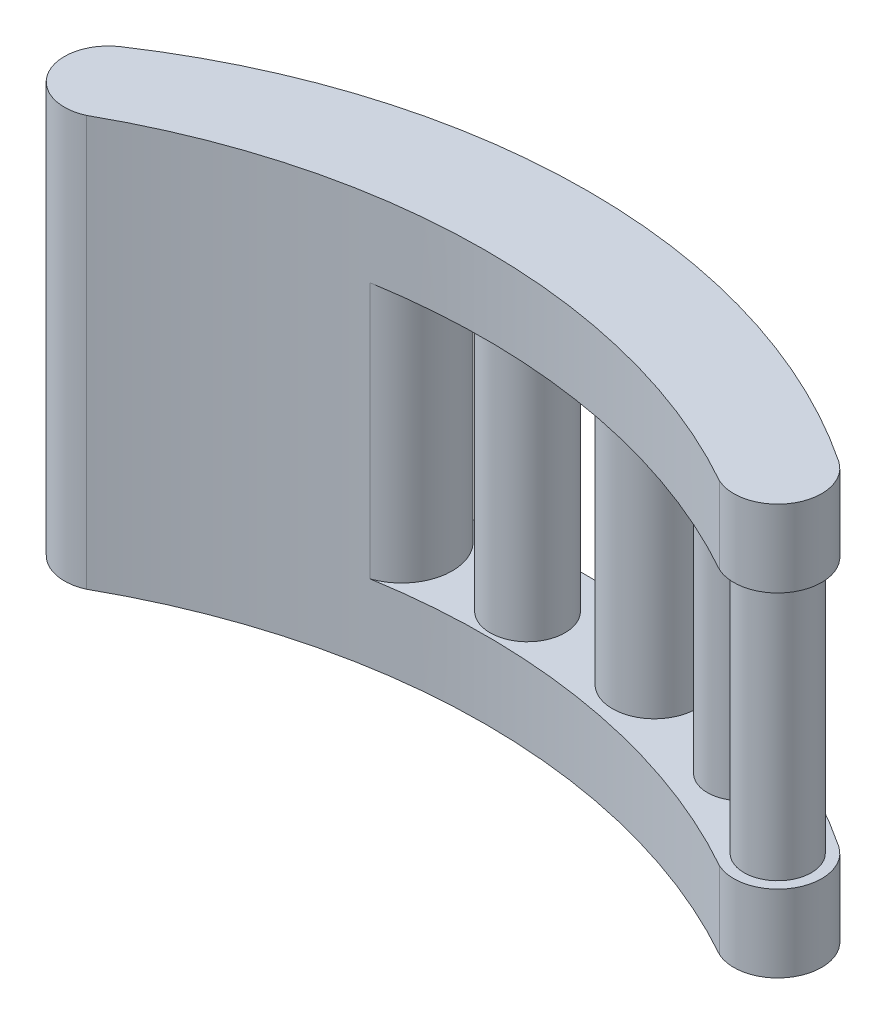
SolidWorks part; units mm, degrees
ref_plane "Front Plane" through (0, 0, 0) normal (0, 0, 1) x (1, 0, 0)
ref_plane "Top Plane" through (0, 0, 0) normal (0, 1, 0) x (1, 0, 0)
ref_plane "Right Plane" through (0, 0, 0) normal (1, 0, 0) x (0, 0, -1)
ref_plane "Plane1" through (0, 20, 0) normal (0, 1, 0) x (1, 0, 0)
sketch "Sketch1" plane through (0, 0, 0) normal (0, 1, 0) x (1, 0, 0)
  line L0 (0, 0) -> (0, -52.5) construction
  line L1 (0, 0) -> (-35, 0) construction
  line L2 (0, 0) -> (35, 0) construction
  line L3 (0, 10.5971) -> (0, 0.5971) construction
  line L4 (0, -52.5) -> (0, -62.5) construction
  line L5 (-35, 0) -> (-35, -10) construction
  line L6 (35, 0) -> (35, -10) construction
  arc A0 (35, 0) -> (-35, 0) centre (0, -52.5) ccw
  arc A1 (30.8661, -7.4679) -> (-30.8661, -7.4679) centre (0, -62.5) ccw
  arc A2 (-35, 0) -> (-30.2491, -7.1263) centre (-32.6246, -3.5632) ccw
  arc A3 (35, 0) -> (30.2491, -7.1263) centre (32.6246, -3.5632) cw
  dimension "D1" = 52.5
  dimension "D2" = 35
  dimension "D3" = 35
  dimension "D4" = 10
  dimension "D5" = 10
  dimension "D6" = 10
extrude "Boss-Extrude1" add sketch "Sketch1" along normal blind 7.5 contours A3 A0 A2 A1 region at (0, 0, -2.1659)
sketch "Sketch2" plane through (0, 7.5, 0) normal (0, 1, 0) x (1, 0, 0)
  circle A0 centre (32.6246, -3.5632) radius 3.2809
  circle A1 centre (24.0877, 1.4023) radius 3.2752
  circle A2 centre (12.37, 4.6775) radius 4.0969
  circle A3 centre (0, 4.6775) radius 3.6479
  arc A4 (35, 0) -> (-35, 0) centre (0, -52.5) ccw construction
  arc A5 (-12.8862, 9.2673) -> (-11.1401, -0.4572) centre (-12.0132, 4.405) cw
  point P7 (-12.8862, 9.2673)
  arc M2 (35, 0) -> (-35, 0) centre (0, -52.5) ccw
  arc M3 (-35, 0) -> (-30.8661, -7.4679) centre (-32.6246, -3.5632) ccw
  arc M4 (-30.8661, -7.4679) -> (30.8661, -7.4679) centre (0, -62.5) cw
extrude "Boss-Extrude2" add sketch "Sketch2" along normal blind 12.5 contours A5 M2 M3 M4 | A3 | A2 | A1 | A0 region at (32.6246, 7.5, 3.5632) region at (24.0877, 7.5, -1.4023) region at (12.37, 7.5, -4.6775) region at (0, 7.5, -4.6775) region at (-21.8715, 7.5, -1.1402)
mirror "Mirror1" about plane through (0, 20, 0) normal (0, 1, 0) of "Boss-Extrude1", "Boss-Extrude2"
